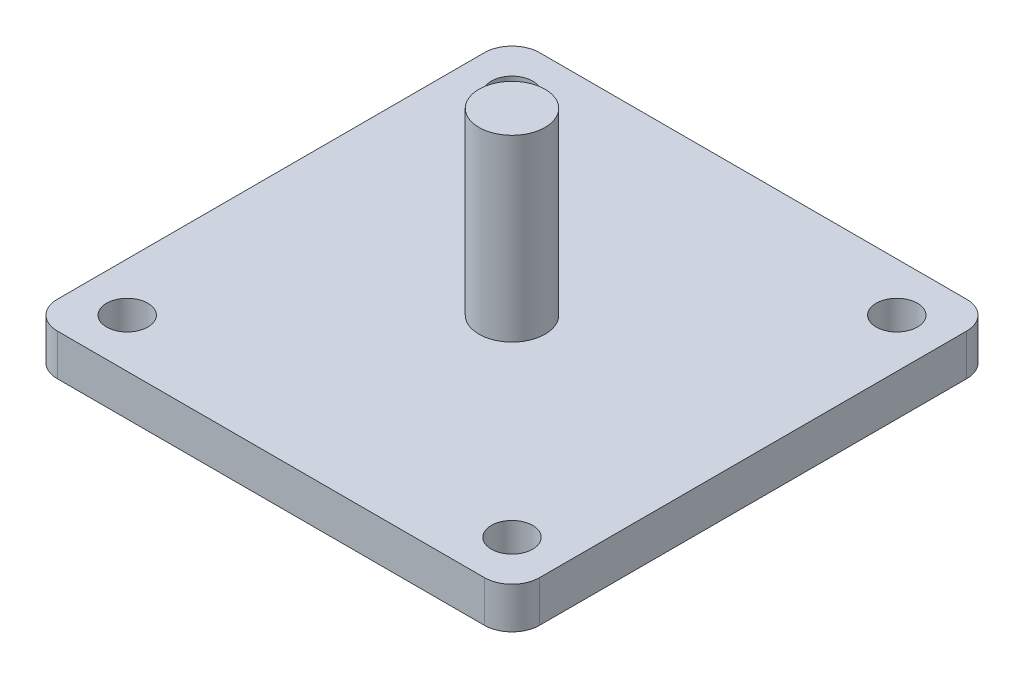
SolidWorks part; units mm, degrees
ref_plane "Plano frontal" through (0, 0, 0) normal (0, 0, 1) x (1, 0, 0)
ref_plane "Plano superior" through (0, 0, 0) normal (0, 1, 0) x (1, 0, 0)
ref_plane "Plano direito" through (0, 0, 0) normal (1, 0, 0) x (0, 0, -1)
sketch "Esboço1" plane through (0, 0, 0) normal (0, 1, 0) x (1, 0, 0)
  line L1 (-17.5, -17.5) -> (17.5, -17.5)
  line L2 (-17.5, -17.5) -> (-17.5, 17.5)
  line L3 (-17.5, 17.5) -> (17.5, 17.5)
  line L4 (17.5, -17.5) -> (17.5, 17.5)
  line L5 (-17.5, -17.5) -> (17.5, 17.5) construction
  line L6 (-17.5, 17.5) -> (17.5, -17.5) construction
  point P0 (0, 0)
  dimension "D1" = 35
  dimension "D2" = 35
extrude "Ressalto-extrusão1" add sketch "Esboço1" along normal mid plane 3
fillet "Filete1" radius 2 4 edges at (-17.5, 0, 17.5) (-17.5, 0, -17.5) (17.5, 0, -17.5) (17.5, 0, 17.5)
sketch "Esboço2" plane through (0, 1.5, 0) normal (0, 1, 0) x (1, 0, 0)
  circle A0 centre (0, 0) radius 2.4
  dimension "D1" = 4.8
extrude "Ressalto-extrusão2" add sketch "Esboço2" along normal blind 13
sketch "Esboço3" plane through (0, 1.5, 0) normal (0, 1, 0) x (1, 0, 0)
  circle A1 centre (13.9645, 13.9645) radius 1.5
  circle A6 centre (13.9645, -13.9645) radius 1.5
  circle A7 centre (-13.9645, -13.9645) radius 1.5
  circle A8 centre (-13.9645, 13.9645) radius 1.5
  point P12 (0, 0)
extrude "Corte-extrusão1" cut sketch "Esboço3" against normal blind 10
move or copy body "Corpo-Converter em corpo de malha1" [suppressed] bodies to move or copy 103 copy no translate (0, 0, 0) parameters "D1"=0, "D2"=0, "D3"=0
